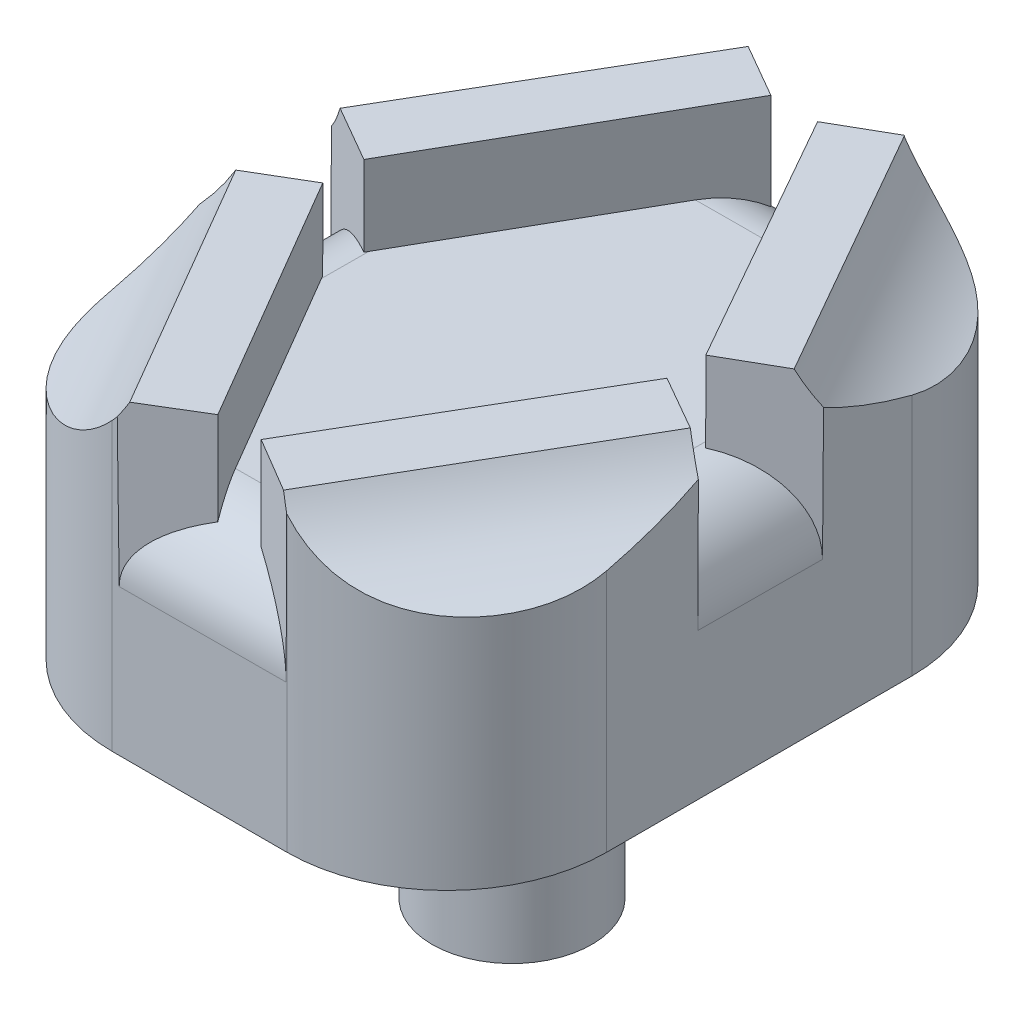
SolidWorks part; units mm, degrees
ref_plane "Front Plane" through (0, 0, 0) normal (0, 0, 1) x (1, 0, 0)
ref_plane "Top Plane" through (0, 0, 0) normal (0, 1, 0) x (1, 0, 0)
ref_plane "Right Plane" through (0, 0, 0) normal (1, 0, 0) x (0, 0, -1)
sketch "Sketch1" plane through (0, 0, 0) normal (0, 1, 0) x (1, 0, 0)
  circle A0 centre (0, 0) radius 5
  dimension "D1" = 10
extrude "Boss-Extrude1" add sketch "Sketch1" along normal blind 15
sketch "Sketch3" plane through (0, 15, 0) normal (0, 1, 0) x (1, 0, 0)
  line L1 (-15.4639, 19.5448) -> (15.4639, 19.5448)
  line L2 (-15.4639, 19.5448) -> (-15.4639, -19.5448)
  line L3 (-15.4639, -19.5448) -> (15.4639, -19.5448)
  line L4 (15.4639, 19.5448) -> (15.4639, -19.5448)
  line L5 (-15.4639, 19.5448) -> (15.4639, -19.5448) construction
  line L6 (-15.4639, -19.5448) -> (15.4639, 19.5448) construction
  point P0 (0, 0)
extrude "Boss-Extrude2" add sketch "Sketch3" along normal offset from surface (14.0591 mm away) 5
sketch "Sketch4" plane through (-0.1324, 29.0908, -0.154) normal (-0.0046, 1, -0.0053) x (1, 0.0046, 0)
  line L0 (-10.4684, 1.1791) -> (-14.0156, 3.2374)
  line L1 (-14.0156, 3.2374) -> (-4.6421, 19.3912)
  line L2 (-15.3319, 19.3913) -> (15.5963, 19.3909) construction
  line L3 (-4.6421, 19.3912) -> (-1.2615, 17.4296)
  line L4 (-1.2615, 17.4296) -> (-10.4684, 1.1791)
  line L5 (1.643, 17.4498) -> (10.9182, 1.1791)
  line L6 (10.9182, 1.1791) -> (14.4396, 3.1864)
  line L7 (14.4396, 3.1864) -> (5.1094, 19.4259)
  line L8 (5.1094, 19.4259) -> (1.643, 17.4498)
  line L9 (-4.5098, -19.4266) -> (-1.072, -17.3562)
  line L10 (-1.072, -17.3562) -> (-10.4684, -1.3925)
  line L11 (-10.4684, -1.3925) -> (-13.8971, -3.4106)
  line L12 (-13.8971, -3.4106) -> (-4.5098, -19.4266)
  line L13 (1.643, -17.3597) -> (5.1094, -19.4266)
  line L14 (5.1094, -19.4266) -> (14.4185, -3.2912)
  line L15 (14.4185, -3.2912) -> (10.9715, -1.3025)
  line L16 (10.9715, -1.3025) -> (1.643, -17.3597)
extrude "Boss-Extrude3" add sketch "Sketch4" along normal blind 5
fillet "Fillet3" radius 10 4 edges at (-9.4612, 28.9885, -11.4679) (9.652, 29.0756, -11.4428) (9.6314, 29.1954, 11.2045) (-9.3358, 29.1093, 11.2647)
fillet "Fillet4" radius 10 4 edges at (15.4637, 22.0296, -19.545) (-15.4642, 21.9592, -19.5447) (-15.4637, 22.0626, 19.545) (15.4642, 22.133, 19.5447)
fillet "Fillet5" radius 5 4 edges at (-15.4639, 29.0217, -0.0267) (0.0707, 28.9891, -19.5448) (15.4639, 29.1621, -0.0919) (0.1698, 29.1964, 19.5448)
